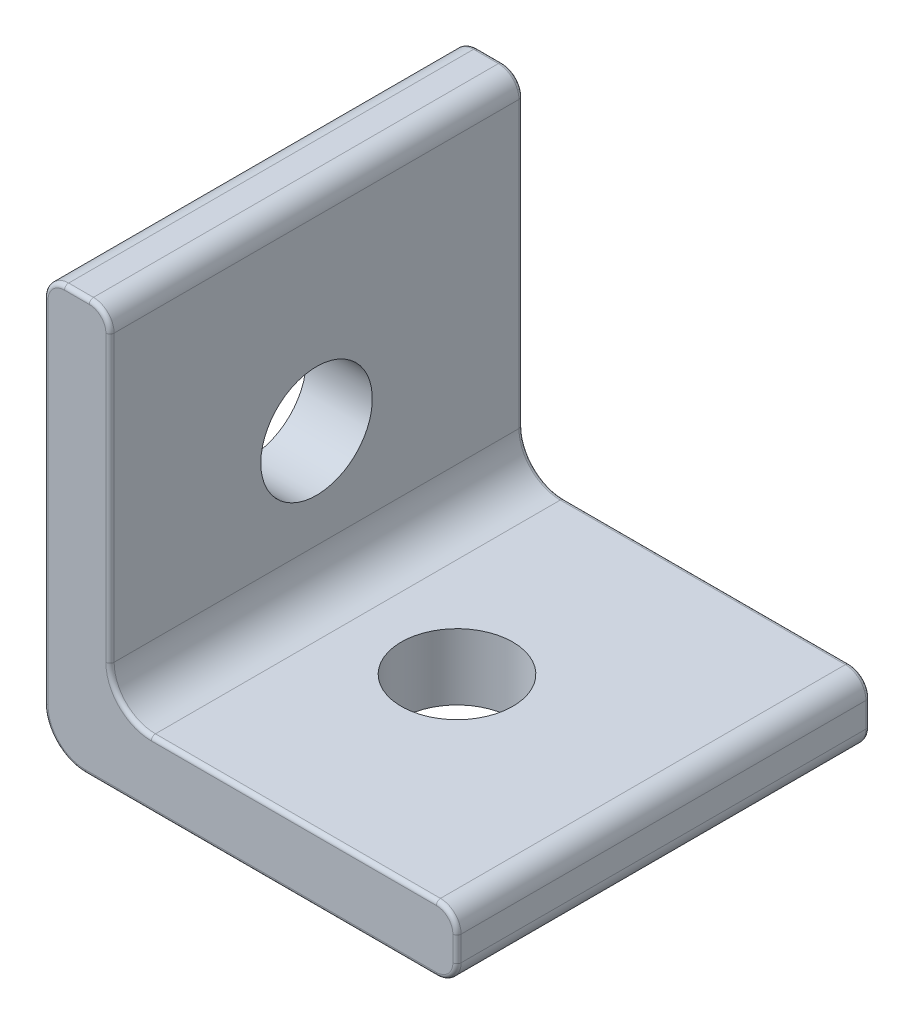
SolidWorks part; units mm, degrees
ref_plane "Front Plane" through (0, 0, 0) normal (0, 0, 1) x (1, 0, 0)
ref_plane "Top Plane" through (0, 0, 0) normal (0, 1, 0) x (1, 0, 0)
ref_plane "Right Plane" through (0, 0, 0) normal (1, 0, 0) x (0, 0, -1)
sketch "Sketch1" plane through (0, 0, 0) normal (0, 0, 1) x (1, 0, 0)
  line L1 (5.6792, 0) -> (19, 0)
  line L3 (5.2, 3.2) -> (19, 3.2)
  line L4 (20, 1) -> (20, 2.2)
  line L5 (2, 0) -> (5.6792, 0)
  line L6 (0, 2) -> (0, 19)
  line L7 (1, 20) -> (2.2, 20)
  line L8 (3.2, 5.2) -> (3.2, 19)
  arc A0 (3.2, 5.2) -> (5.2, 3.2) centre (5.2, 5.2) ccw
  arc A1 (0, 2) -> (2, 0) centre (2, 2) ccw
  arc A2 (19, 0) -> (20, 1) centre (19, 1) ccw
  arc A3 (19, 3.2) -> (20, 2.2) centre (19, 2.2) cw
  arc A4 (2.2, 20) -> (3.2, 19) centre (2.2, 19) cw
  arc A5 (0, 19) -> (1, 20) centre (1, 19) cw
  point P12 (0, 0)
  point P15 (20, 0)
  point P18 (20, 3.2)
  point P21 (3.2, 20)
  point P24 (0, 20)
  dimension "D5" = 2
  dimension "D6" = 1
  dimension "D1" = 20
  dimension "D2" = 20
  dimension "D3" = 3.2
  dimension "D4" = 3.2
extrude "Boss-Extrude1" add sketch "Sketch1" along normal blind 20
fillet "Fillet1" radius 0.2 24 edges at (3.2, 12.1, 0) (2.9071, 19.7071, 0) (1.6, 20, 0) (0.2929, 19.7071, 0) (0, 10.5, 0) (0.5858, 0.5858, 0) (10.5, 0, 0) (19.7071, 0.2929, 0) (20, 1.6, 0) (19.7071, 2.9071, 0) (12.1, 3.2, 0) (3.7858, 3.7858, 0) (12.1, 3.2, 20) (19.7071, 2.9071, 20) (20, 1.6, 20) (19.7071, 0.2929, 20) (10.5, 0, 20) (0.5858, 0.5858, 20) (0, 10.5, 20) (0.2929, 19.7071, 20) (1.6, 20, 20) (2.9071, 19.7071, 20) (3.2, 12.1, 20) (3.7858, 3.7858, 20)
sketch "Sketch2" plane through (0, 0, 0) normal (-1, 0, 0) x (0, 0, 1)
  line L0 (10, 20) -> (10, 0) construction
  line L1 (19.8, 20) -> (0.2, 20) construction
  line L2 (19.8, 0) -> (0.2, 0) construction
  circle A0 centre (10, 10) radius 2.7
  dimension "D1" = 5.4
extrude "Cut-Extrude1" cut sketch "Sketch2" against normal up to surface (3.2 mm away) up to face at (3.2, 12.1, 10)
sketch "Sketch3" plane through (0, 0, 0) normal (0, -1, 0) x (1, 0, 0)
  line L0 (20, 10) -> (0, 10) construction
  line L1 (20, 19.8) -> (20, 0.2) construction
  line L2 (0, 19.8) -> (0, 0.2) construction
  circle A0 centre (10, 10) radius 2.7
  dimension "D1" = 5.4
extrude "Cut-Extrude2" cut sketch "Sketch3" against normal up to surface (3.2 mm away) up to face at (12.1, 3.2, 10)
equation "\"D4@Sketch1\"=\"D3@Sketch1\""
